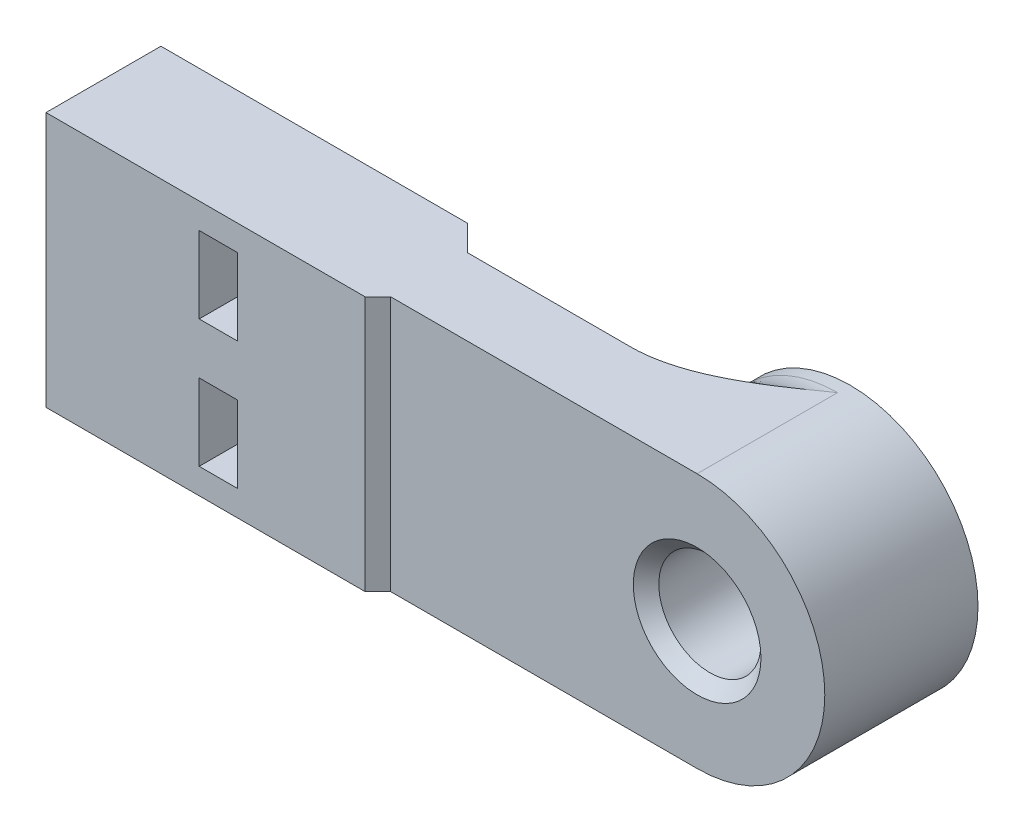
SolidWorks part; units mm, degrees
ref_plane "Спереди" through (0, 0, 0) normal (0, 0, 1) x (1, 0, 0)
ref_plane "Сверху" through (0, 0, 0) normal (0, 1, 0) x (1, 0, 0)
ref_plane "Справа" through (0, 0, 0) normal (1, 0, 0) x (0, 0, -1)
sketch "Эскиз1" plane through (0, 0, 0) normal (0, 0, 1) x (1, 0, 0)
  line L0 (0, 0) -> (-50, 0) construction
  line L2 (0, 10) -> (-50, 10)
  line L3 (0, 10) -> (0, -10)
  line L4 (0, -10) -> (-50, -10)
  line L5 (-50, 10) -> (-50, -10)
  circle A0 centre (0, 0) radius 10
  circle A1 centre (0, 0) radius 4
  dimension "D2" = 20
  dimension "D3" = 8
  dimension "D1" = 50
extrude "Бобышка-Вытянуть1" add sketch "Эскиз1" along normal blind 6 contours A1 L3 A0 | L0 A1 L3 A0 | A1 L0 A0 L3 | A0 L0 L5 L4 | L0 A0 L2 L5 region at (-4.7292, -4.7292, 0) region at (-4.7292, 4.7292, 0) region at (4.7292, 0, 0) region at (-28.8679, -5.1409, 0) region at (-28.8679, 5.1409, 0)
sketch "Эскиз3" plane through (-50, 0, 0) normal (-1, 0, 0) x (0, 0, 1)
  line L0 (6, 10) -> (6, -10) construction
  line L1 (6, 10) -> (6, -10)
  line L2 (6, 0) -> (0, 0) construction
  line L3 (0, 10) -> (0, -10) construction
  line L4 (0, 10) -> (0, -10)
  circle A0 centre (2.2, 5) radius 1.5
  circle A1 centre (2.2, -5) radius 1.5
  dimension "D1" = 10
  dimension "D2" = 3
  dimension "D3" = 2.2
extrude "Вырез-Вытянуть2" cut sketch "Эскиз3" against normal blind 20 contours A0 | A1 region at (-50, 5, 2.2) region at (-50, -5, 2.2)
sketch "Эскиз4" plane through (0, 0, 0) normal (0, 1, 0) x (1, 0, 0)
  line L0 (0, 0) -> (-50, 0) construction
  line L1 (0, 0) -> (-50, 0)
  line L2 (-50, 0) -> (-50, 2)
  line L3 (-50, 2) -> (-26, 2)
  line L4 (-26, 2) -> (-24, 0)
  dimension "D1" = 2
  dimension "D2" = 135
  dimension "D3" = 24
extrude "Бобышка-Вытянуть2" add sketch "Эскиз4" along normal mid plane 20 contours L4 L3 L2 L1 region at (-37.4933, 0, -0.9867)
sketch "Эскиз6" plane through (0, 0, 0) normal (0, 1, 0) x (1, 0, 0)
  line L0 (-26, 2) -> (-24, 0) construction
  line L1 (-26, 2) -> (-24, 0)
  line L2 (-50, -6) -> (-50, 2) construction
  line L3 (-50, -6) -> (-50, 2)
  line L4 (-50, -6) -> (-50, -7)
  line L5 (-50, -7) -> (-25, -7)
  line L6 (-25, -7) -> (-24, -6)
  line L7 (0, -6) -> (-50, -6) construction
  line L8 (0, -6) -> (-50, -6)
  dimension "D1" = 1
  dimension "D2" = 135
extrude "Бобышка-Вытянуть3" add sketch "Эскиз6" along normal mid plane 20 contours L6 L8 L4 L5 region at (-37.2484, 0, 6.4967)
extrude "Бобышка-Вытянуть4" add sketch "Эскиз1<3>" against normal blind 6 contours A1 L3 A0 | L0 A1 L3 A0 | A1 L0 A0 L3 region at (-4.7292, -4.7292, 0) region at (-4.7292, 4.7292, 0) region at (4.7292, 0, 0)
sketch "Эскиз1<3>" plane through (0, 0, 0) normal (0, 0, 1) x (1, 0, 0) same geometry as "Эскиз1"
sketch "Эскиз5" plane through (0, 0, -2) normal (0, 0, -1) x (-1, 0, 0)
  line L0 (50, 0) -> (26, 0) construction
  line L1 (50, 10) -> (50, -10) construction
  line L2 (26, 10) -> (26, -10) construction
  line L3 (35, -5) -> (38, -5) construction
  line L4 (38, -8) -> (35, -8)
  line L5 (38, -8) -> (38, -2)
  line L6 (38, -2) -> (35, -2)
  line L7 (35, -8) -> (35, -2)
  line L8 (38, 8) -> (35, 8)
  line L9 (38, 8) -> (38, 2)
  line L10 (38, 2) -> (35, 2)
  line L11 (35, 8) -> (35, 2)
  line L12 (38, 5) -> (35, 5) construction
  dimension "D1" = 6
  dimension "D2" = 6
  dimension "D3" = 5
  dimension "D4" = 3
  dimension "D5" = 3
  dimension "D6" = 15
extrude "Вырез-Вытянуть3" cut sketch "Эскиз5" against normal through all
chamfer "Фаска1" distance 1 angle 45 2 edges at (4, 0, 6) (4, 0, -6)
fillet "Скругление1" radius 5 1 edges at (-10, 0, 0)
